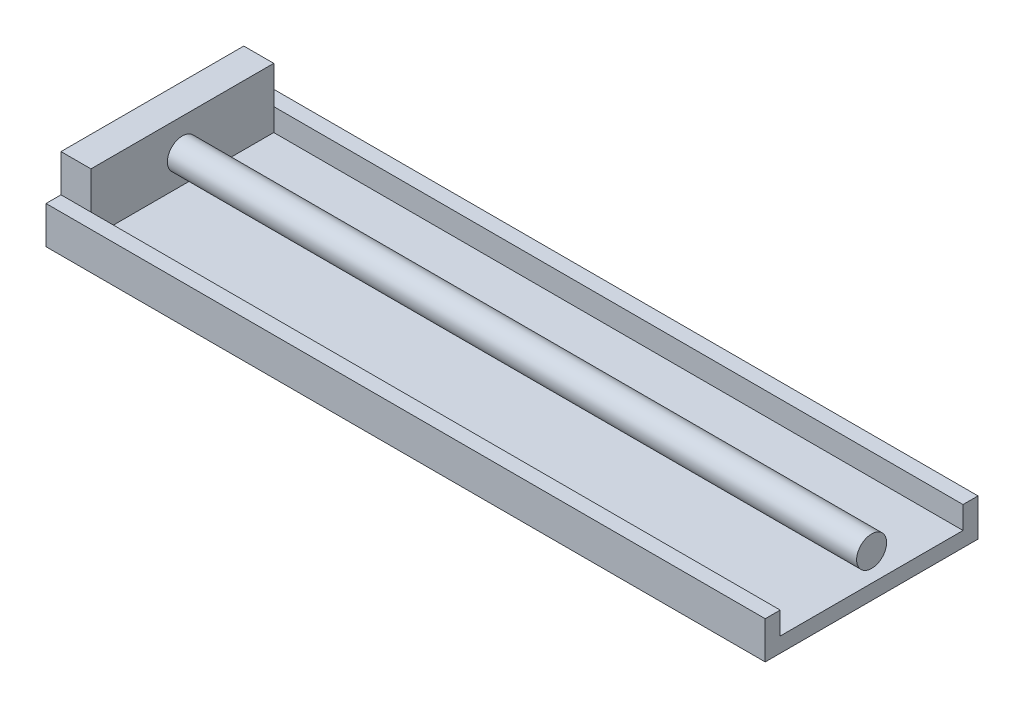
SolidWorks part; units mm, degrees
ref_plane "Front Plane" through (0, 0, 0) normal (0, 0, 1) x (1, 0, 0)
ref_plane "Top Plane" through (0, 0, 0) normal (0, 1, 0) x (1, 0, 0)
ref_plane "Right Plane" through (0, 0, 0) normal (1, 0, 0) x (0, 0, -1)
sketch "Sketch1" plane through (0, 0, 0) normal (0, 1, 0) x (1, 0, 0)
  line L1 (-120, -30.5) -> (120, -30.5)
  line L2 (-120, -30.5) -> (-120, 30.5)
  line L3 (-120, 30.5) -> (120, 30.5)
  line L4 (120, -30.5) -> (120, 30.5)
  line L5 (-120, -30.5) -> (120, 30.5) construction
  line L6 (-120, 30.5) -> (120, -30.5) construction
  point P0 (0, 0)
  dimension "D1" = 61
  dimension "D2" = 240
extrude "Boss-Extrude1" add sketch "Sketch1" along normal blind 5
sketch "Sketch2" plane through (0, 5, 0) normal (0, 1, 0) x (1, 0, 0)
  line L0 (-120, -30.5) -> (120, -30.5) construction
  line L1 (-120, 30.5) -> (-110, 30.5)
  line L2 (-120, 30.5) -> (-120, -30.5)
  line L3 (-120, -30.5) -> (-110, -30.5)
  line L4 (-110, 30.5) -> (-110, -30.5)
  dimension "D1" = 10
extrude "Boss-Extrude2" add sketch "Sketch2" along normal blind 20
sketch "Sketch3" plane through (-110, 0, 0) normal (1, 0, 0) x (0, 0, -1)
  line L0 (0, 5) -> (0, 14.27) construction
  line L1 (-30.5, 5) -> (30.5, 5) construction
  circle A0 centre (0, 14.27) radius 5
  dimension "D2" = 10
  dimension "D1" = 9.27
extrude "Boss-Extrude3" add sketch "Sketch3" along normal through all
sketch "Sketch5" plane through (0, 0, 30.5) normal (0, 0, 1) x (1, 0, 0)
  line L0 (-120, 25) -> (-120, 0) construction
  line L1 (-120, 12.5) -> (120, 12.5)
  line L2 (-120, 12.5) -> (-120, 0)
  line L3 (-120, 0) -> (120, 0)
  line L4 (120, 12.5) -> (120, 0)
extrude "Boss-Extrude4" add sketch "Sketch5" along normal blind 5
sketch "Sketch6" plane through (0, 0, -30.5) normal (0, 0, -1) x (-1, 0, 0)
  line L1 (120, 12.5) -> (-120, 12.5)
  line L2 (120, 12.5) -> (120, 0)
  line L3 (120, 0) -> (-120, 0)
  line L4 (-120, 12.5) -> (-120, 0)
extrude "Boss-Extrude5" add sketch "Sketch6" along normal blind 5
